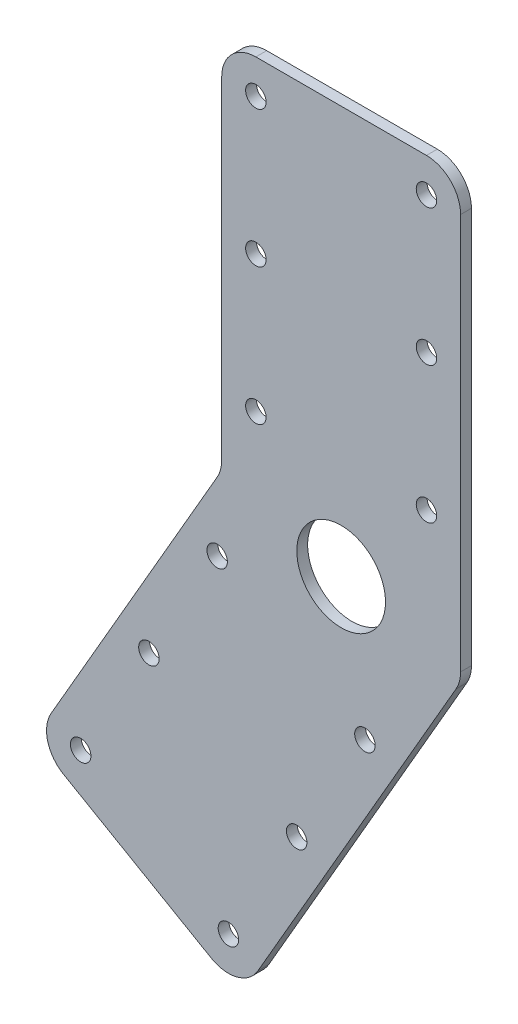
SolidWorks part; units mm, degrees
material "6061 Alloy"
ref_plane "Front Plane" through (0, 0, 0) normal (0, 0, 1) x (1, 0, 0)
ref_plane "Top Plane" through (0, 0, 0) normal (0, 1, 0) x (1, 0, 0)
ref_plane "Right Plane" through (0, 0, 0) normal (1, 0, 0) x (0, 0, -1)
sketch "Sketch1" plane through (0, 0, 0) normal (0, 0, 1) x (1, 0, 0)
  line L0 (0, 0) -> (0, 55)
  line L1 (0, 55) -> (35, 55)
  line L2 (35, 55) -> (35, -9.3782)
  line L3 (35, -9.3782) -> (2.8109, -65.1314)
  line L4 (2.8109, -65.1314) -> (-27.5, -47.6314)
  line L5 (-27.5, -47.6314) -> (0, 0)
  line L6 (0, 0) -> (35, -9.3782) construction
  line L7 (5, 55) -> (5, 0) construction
  line L8 (0, 0) -> (5, 0) construction
  line L9 (5, 50) -> (5, 55) construction
  line L10 (17.5, 55) -> (17.5, -4.6891) construction
  line L11 (-23.1699, -50.1314) -> (4.3301, -2.5) construction
  line L12 (0, 0) -> (4.3301, -2.5) construction
  line L13 (0, 27.5) -> (5, 30) construction
  line L15 (-12.3446, -56.3814) -> (17.5, -4.6891) construction
  line L16 (17.5, -4.6891) -> (10.1554, -17.4103) construction
  line L17 (10.1554, -17.4103) -> (20.9808, -23.6603) construction
  circle A0 centre (17.5, -4.6891) radius 6.5
  circle A1 centre (5, 50) radius 1.5
  circle A2 centre (5, 30) radius 1.5
  circle A3 centre (5, 10) radius 1.5
  circle A4 centre (30, 10) radius 1.5
  circle A5 centre (30, 30) radius 1.5
  circle A6 centre (30, 50) radius 1.5
  circle A7 centre (-20.6699, -45.8013) radius 1.5
  circle A8 centre (-10.6699, -28.4808) radius 1.5
  circle A9 centre (-0.6699, -11.1603) radius 1.5
  circle A10 centre (20.9808, -23.6603) radius 1.5
  circle A11 centre (10.9808, -40.9808) radius 1.5
  circle A12 centre (0.9808, -58.3013) radius 1.5
  dimension "D5" = 13
  dimension "D7" = 3
  dimension "D9" = 20
  dimension "D10" = 20
  dimension "D11" = 5
  dimension "D1" = 35
  dimension "D2" = 55
  dimension "D3" = 55
  dimension "D4" = 150
  dimension "D6" = 5
  dimension "D8" = 5
  dimension "D12" = 20
  dimension "D13" = 20
extrude "Boss-Extrude1" add sketch "Sketch1" along normal blind 1.5875
fillet "Fillet1" radius 5 6 edges at (35, -9.3782, 0.7937) (0, 0, 0.7937) (2.8109, -65.1314, 0.7937) (-27.5, -47.6314, 0.7937) (0, 55, 0.7937) (35, 55, 0.7937)
